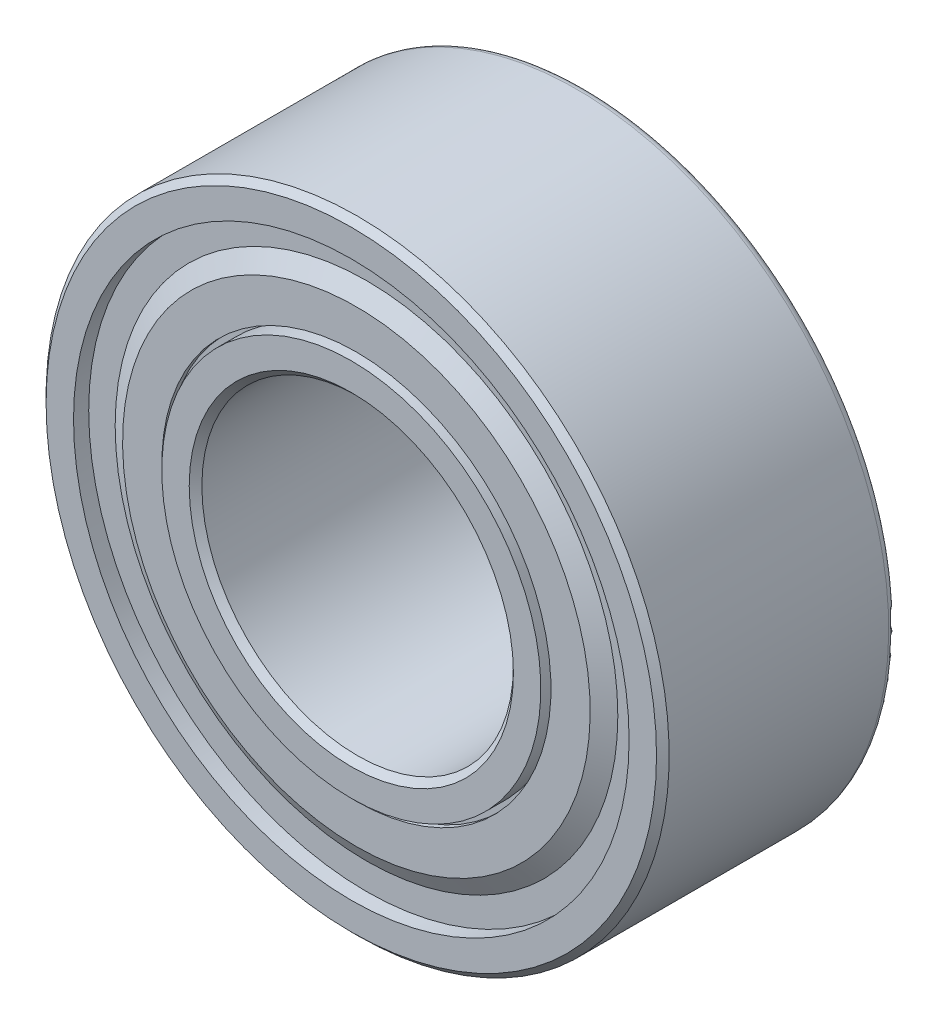
SolidWorks part; units mm, degrees
ref_plane "Front Plane" through (0, 0, 0) normal (0, 0, 1) x (1, 0, 0)
ref_plane "Top Plane" through (0, 0, 0) normal (0, 1, 0) x (1, 0, 0)
ref_plane "Right Plane" through (0, 0, 0) normal (1, 0, 0) x (0, 0, -1)
sketch "Sketch1" plane through (0, 0, 0) normal (1, 0, 0) x (0, 0, -1)
  line L0 (0, 4) -> (0, -4) construction
  line L1 (-1.5, 4) -> (1.5, 4) construction
  line L2 (0, 0) -> (1.5, 0) construction
  line L3 (1.5, 4.6) -> (1.5, -4.6) construction
  line L4 (1.5, -4.6) -> (0.9, -4.6) construction
  line L5 (1.5, 2) -> (0, 2) construction
  line L6 (1.5, 2) -> (1.5, -2) construction
  dimension "OD" = 8
  dimension "Width" = 3
  dimension "Flange Thickness" = 0.6
  dimension "ID" = 4
  dimension "Flange OD" = 9.2
sketch "Sketch2" plane through (0, 0, 0) normal (1, 0, 0) x (0, 0, -1)
  line L0 (1.5, 4.6) -> (0.9, 4.6)
  line L1 (0.9, 4.6) -> (0.9, 4.2652)
  line L2 (0.6348, 4) -> (-1.5, 4)
  line L3 (-1.5, 4) -> (-1.5, 3.35)
  line L4 (-1.5, 3.35) -> (-0.4873, 3.35)
  line L5 (1.5, 4.6) -> (1.5, -4.6) construction
  line L6 (1.5, 3.35) -> (1.5, 4.6)
  line L7 (1.5, 2) -> (-1.5, 2)
  line L8 (-1.5, 2) -> (-1.5, 2.65)
  line L9 (-1.5, 2.65) -> (-0.4873, 2.65)
  line L10 (1.5, 2.65) -> (1.5, 2)
  line L11 (0, 4) -> (0, 2) construction
  line L12 (-0.6, 3) -> (0.6, 3) construction
  line L13 (0.4873, 3.35) -> (1.5, 3.35)
  line L14 (0.4873, 2.65) -> (1.5, 2.65)
  line L15 (0.9, 4.2652) -> (1.0326, 4.1326)
  line L16 (1.0326, 4.1326) -> (1.0326, 3.8674)
  line L17 (1.0326, 3.8674) -> (0.7674, 3.8674)
  line L18 (0.7674, 3.8674) -> (0.6348, 4)
  line L19 (0.9, 4) -> (1.0326, 3.8674) construction
  line L20 (1.0326, 4.1326) -> (0.7674, 3.8674) construction
  line L21 (0.6348, 4) -> (0.9, 4) construction
  line L22 (0.9, 4) -> (0.9, 4.2652) construction
  line L23 (-1.5, 0) -> (1.5, 0) construction
  circle A0 centre (0, 3) radius 0.6 construction
  arc A1 (-0.4873, 3.35) -> (0.4873, 3.35) centre (0, 3) cw
  arc A2 (-0.4873, 2.65) -> (0.4873, 2.65) centre (0, 3) ccw
  dimension "Ball Dia." = 1.2
  dimension "D2" = 135
  dimension "D3" = 0.375
  dimension "Race Thikness" = 0.65
  dimension "D4" = 0.7
revolve "Revolve1" add sketch "Sketch2" angle 360 about L2
fillet "Fillet1" radius 0.0813 3 edges at (0, -4.6, -1.5) (0, -4.6, -0.9) (0, -4, 1.5) profile chamfer
sketch "Sketch3" plane through (0, 0, 0) normal (0, 0, 1) x (1, 0, 0)
  line L0 (-2, 0) -> (2, 0) construction
  line L1 (-4, 0) -> (4, 0) construction
  point P5 (0, 0)
  dimension "ID2" = 4
  dimension "OD2" = 8
fillet "Fillet2" radius 0.0813 2 edges at (0, -2, -1.5) (0, -2, 1.5) profile chamfer
sketch "Sketch7" plane through (0, 0, 0) normal (0, 0, 1) x (1, 0, 0)
  line L0 (0, 3.6) -> (0, 2.4)
  line L1 (0, 4.6) -> (0, -4.6) construction
  line L2 (-0.7348, 3.6) -> (0, 0) construction
  line L3 (0, 0) -> (0.7348, 3.6) construction
  line L4 (0.7348, 3.6) -> (-0.7348, 3.6) construction
  circle A0 centre (0, 3) radius 0.6 construction
  circle A1 centre (0, 0) radius 3.6 construction
  circle A2 centre (0, 0) radius 2.4 construction
  arc A4 (0, 3.6) -> (0, 2.4) centre (0, 3) ccw
  dimension "D1" = 23.074
revolve "Revolve3" add sketch "Sketch7" angle 360 about L0
pattern_circular "CirPattern3" count 12 over 360 about axis through (0, 0, 0) along (0, 0, 1) of bodies 107
sketch "Sketch8" plane through (0, 0, 0) normal (1, 0, 0) x (0, 0, -1)
  line L1 (-1.5, 3.35) -> (-1.24, 3.35)
  line L2 (-1.5, 3.35) -> (-1.5, 3.5667)
  line L3 (-1.5, 3.5667) -> (-1.24, 3.5667)
  line L4 (-1.24, 3.35) -> (-1.24, 3.5667)
  line L5 (1.5, 3.35) -> (1.24, 3.35)
  line L6 (1.5, 3.35) -> (1.5, 3.5667)
  line L7 (1.5, 3.5667) -> (1.24, 3.5667)
  line L8 (1.24, 3.35) -> (1.24, 3.5667)
  line L9 (1.5, 2.65) -> (1.24, 2.65)
  line L10 (1.5, 2.65) -> (1.5, 2.4333)
  line L11 (1.5, 2.4333) -> (1.24, 2.4333)
  line L12 (1.24, 2.65) -> (1.24, 2.4333)
  line L13 (-1.5, 2.65) -> (-1.24, 2.65)
  line L14 (-1.5, 2.65) -> (-1.5, 2.4333)
  line L15 (-1.5, 2.4333) -> (-1.24, 2.4333)
  line L16 (-1.24, 2.65) -> (-1.24, 2.4333)
  dimension "D1" = 0.2167
  dimension "D2" = 0.26
revolve "Cut-Revolve1" cut sketch "Sketch8" angle 360 about L2
sketch "Sketch9" plane through (0, 0, 0) normal (1, 0, 0) x (0, 0, -1)
  line L0 (-1.24, 3.5667) -> (-1.24, 3.2095)
  line L1 (-1.24, 3.2095) -> (-1.37, 2.9844)
  line L2 (-1.37, 2.9844) -> (-1.37, 2.4983)
  line L3 (1.37, 2.4983) -> (1.37, 2.4333) construction
  line L4 (1.24, 3.5667) -> (1.24, 3.2095)
  line L5 (1.24, 3.2095) -> (1.37, 2.9844)
  line L6 (1.37, 2.9844) -> (1.37, 2.4983)
  line L7 (1.5, 2.4333) -> (1.24, 2.4333) construction
  line L8 (-1.305, 3.5667) -> (-1.305, 3.2269)
  line L9 (-1.305, 3.2269) -> (-1.435, 3.0018)
  line L10 (-1.435, 3.0018) -> (-1.435, 2.4983)
  line L11 (-1.24, 3.5667) -> (-1.305, 3.5667)
  line L12 (-1.37, 2.4983) -> (-1.435, 2.4983)
  line L13 (1.305, 3.5667) -> (1.305, 3.2269)
  line L14 (1.305, 3.2269) -> (1.435, 3.0018)
  line L15 (1.435, 3.0018) -> (1.435, 2.4983)
  line L16 (1.24, 3.5667) -> (1.305, 3.5667)
  line L17 (1.37, 2.4983) -> (1.435, 2.4983)
  line L18 (-1.24, 3.2095) -> (-1.24, 2.5308) construction
  line L19 (1.24, 3.2095) -> (1.24, 3.5667) construction
  line L20 (-1.24, 2.4333) -> (-1.5, 2.4333) construction
  line L22 (-1.37, 2.4983) -> (-1.37, 2.4333) construction
  dimension "D2" = 150
  dimension "D1" = 150
  dimension "D5" = 0.26
  dimension "D3" = 0.065
  dimension "D4" = 0.065
  dimension "D6" = 0.3571
revolve "Revolve4" add sketch "Sketch9" angle 360 about L2
sketch "Sketch10" plane through (0, 0, 1.5) normal (0, 0, 1) x (1, 0, 0)
  circle A0 centre (0, 0) radius 4.6
  circle A2 centre (0, 0) radius 4
  dimension "D1" = 9.2
  dimension "D2" = 8
extrude "Cut-Extrude1" cut sketch "Sketch10" against normal through all both and the other way through all
sketch "Sketch11" plane through (0, 0, -1.0326) normal (0, 0, 1) x (1, 0, 0)
  circle A0 centre (0, 0) radius 4
  circle A1 centre (0, 0) radius 3.8674
  dimension "D1" = 7.7348
  dimension "D2" = 8
extrude "Boss-Extrude1" add sketch "Sketch11" along normal up to surface (0.3977 mm away) from surface at 0 contours A0 starting at face at (0, -4, -0.6348)
sketch "Sketch12" plane through (0, 0, -0.6348) normal (0, 0, 1) x (1, 0, 0)
  circle A0 centre (0, 0) radius 2
  dimension "D1" = 4
extrude "Cut-Extrude2" cut sketch "Sketch12" against normal through all both and the other way through all
fillet "Fillet4" radius 0.1 1 edges at (4, 0, -1.5)
equation "\"D1@Fillet1\"=\"Race Thikness@Sketch2\"/8"
equation "\"ID2@Sketch3\" = \"ID@Sketch1\""
equation "\"OD2@Sketch3\" = \"OD@Sketch1\""
equation "\"D1@Fillet2\"=\"Race Thikness@Sketch2\"/8"
equation "\"D1@CirPattern3\"=360/\"D1@Sketch7\"-4"
equation "\"D1@Sketch8\"=\"Race Thikness@Sketch2\"/3"
equation "\"D2@Sketch8\"=\"Race Thikness@Sketch2\"/2.5"
equation "\"D3@Sketch9\"=\"D5@Sketch9\"/4"
equation "\"D4@Sketch9\"=\"D5@Sketch9\"/4"
equation "\"D1@Sketch9\"=\"D2@Sketch9\""
equation "\"Ball Dia.@Sketch2\" = \"D1@Sketch2\"*.5"
equation "\"D4@Sketch2\"=((\"OD@Sketch1\"-\"ID@Sketch1\")/2)*.35"
